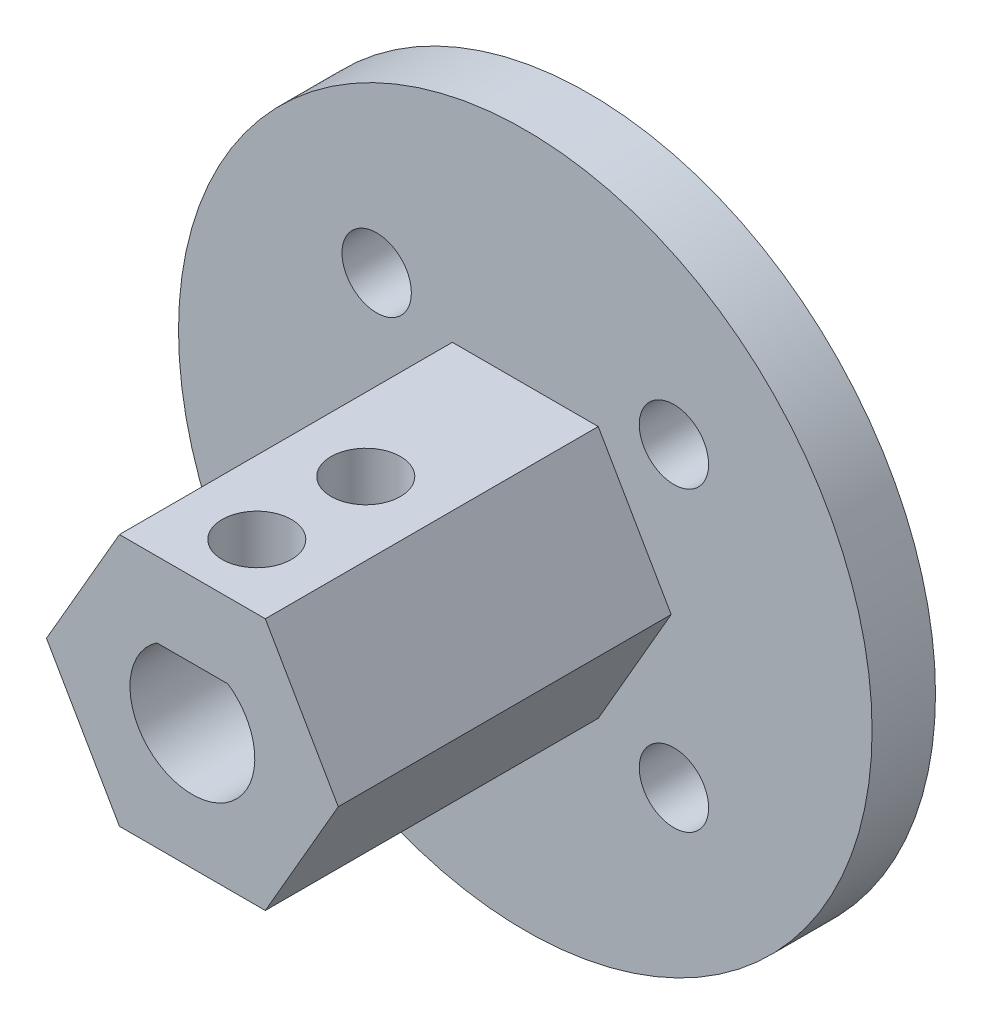
SolidWorks part; units mm, degrees
ref_plane "Alzado" through (0, 0, 0) normal (0, 0, 1) x (1, 0, 0)
ref_plane "Planta" through (0, 0, 0) normal (0, 1, 0) x (1, 0, 0)
ref_plane "Vista lateral" through (0, 0, 0) normal (1, 0, 0) x (0, 0, -1)
sketch "Croquis1" plane through (0, 0, 0) normal (0, 0, 1) x (1, 0, 0)
  line L0 (0, 0) -> (0, 2.5851) construction
  line L1 (7.3617, 0) -> (3.6808, 6.3754)
  line L2 (3.6808, 6.3754) -> (-3.6808, 6.3754)
  line L3 (-3.6808, 6.3754) -> (-7.3617, 0)
  line L4 (-7.3617, 0) -> (-3.6808, -6.3754)
  line L5 (-3.6808, -6.3754) -> (3.6808, -6.3754)
  line L6 (3.6808, -6.3754) -> (7.3617, 0)
  line L7 (-1.8, 2.5851) -> (1.8, 2.5851)
  circle A0 centre (0, 0) radius 6.3754 construction
  arc A1 (-1.8, 2.5851) -> (1.8, 2.5851) centre (0, 0) ccw
  point P14 (0, 2.5851)
  dimension "D2" = 6.3
  dimension "D1" = 12.7508
  dimension "D3" = 3.6
extrude "Saliente-Extruir1" add sketch "Croquis1" along normal blind 20
sketch "Croquis2" plane through (0, 6.3754, 0) normal (0, 1, 0) x (1, 0, 0)
  line L0 (0, -20) -> (0, -16.75) construction
  line L1 (3.6808, -20) -> (-3.6808, -20) construction
  line L2 (0, -16.75) -> (0, -15) construction
  line L3 (0, -15) -> (0, -13) construction
  line L4 (0, -13) -> (0, -11.25) construction
  line L5 (0, -11.25) -> (0, -8) construction
  circle A0 centre (0, -16.75) radius 1.75
  circle A1 centre (0, -11.25) radius 1.75
  dimension "D1" = 3.5
  dimension "D2" = 12
  dimension "D3" = 2
extrude "Cortar-Extruir1" cut sketch "Croquis2" against normal blind 7.5
sketch "Croquis3" plane through (0, 0, 0) normal (0, 0, -1) x (-1, 0, 0)
  circle A0 centre (0, 0) radius 17.5
  dimension "D1" = 35
extrude "Saliente-Extruir2" add sketch "Croquis3" against normal blind 3.2
sketch "Croquis5" plane through (0, 0, 0) normal (0, 0, -1) x (-1, 0, 0)
  line L0 (0, 0) -> (0, 7.5) construction
  line L1 (0, 7.5) -> (-7.5, 7.5) construction
  circle A0 centre (-7.5, 7.5) radius 1.75
  circle A1 centre (7.5, 7.5) radius 1.75
  circle A2 centre (7.5, -7.5) radius 1.75
  circle A3 centre (-7.5, -7.5) radius 1.75
  point P14 (0, 0)
  dimension "D3" = 3.5
  dimension "D1" = 7.5
  dimension "D2" = 7.5
  dimension "D5" = 15
  dimension "D4" = 4
extrude "Cortar-Extruir2" cut sketch "Croquis5" against normal blind 5 and the other way through all
